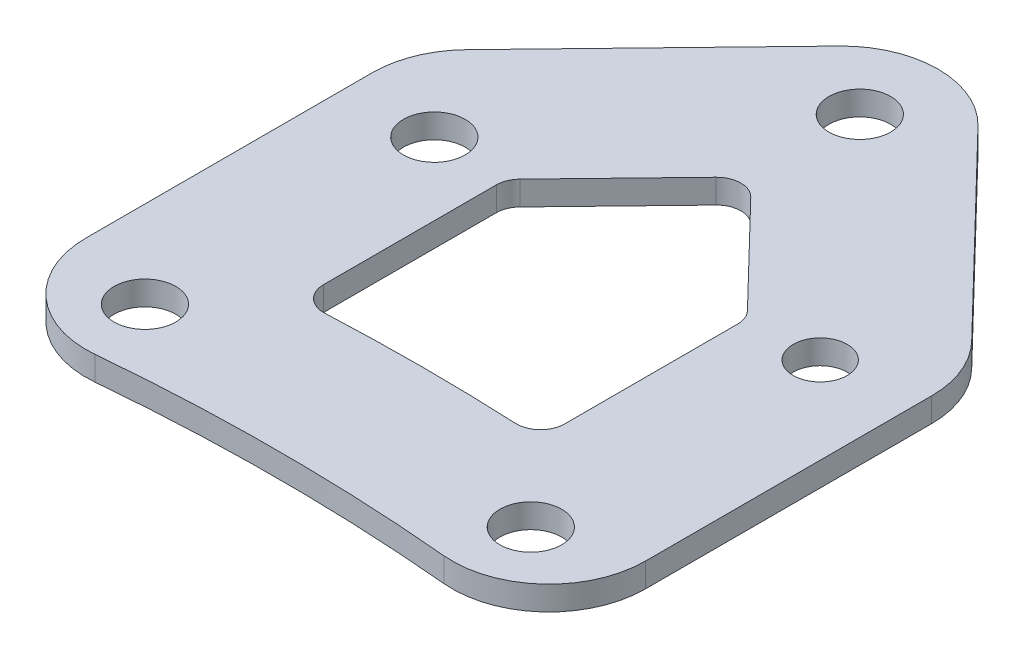
SolidWorks part; units mm, degrees
ref_plane "Front Plane" through (0, 0, 0) normal (0, 0, 1) x (1, 0, 0)
ref_plane "Top Plane" through (0, 0, 0) normal (0, 1, 0) x (1, 0, 0)
ref_plane "Right Plane" through (0, 0, 0) normal (1, 0, 0) x (0, 0, -1)
sketch "Sketch1" plane through (0, 0, 0) normal (0, 1, 0) x (1, 0, 0)
  line L1 (0, 0) -> (18.415, -19.05)
  line L2 (18.415, -19.05) -> (18.415, -47.625)
  line L4 (-18.415, -47.625) -> (-18.415, -19.05)
  line L5 (-18.415, -19.05) -> (0, 0)
  arc A0 (-18.415, -47.625) -> (18.415, -47.625) centre (0, -171.7322) cw
  dimension "D2" = 125.466
  dimension "D1" = 47.625
  dimension "D3" = 36.83
  dimension "D4" = 19.05
extrude "Boss-Extrude1" add sketch "Sketch1" along normal blind 1.5875
sketch "Sketch3" plane through (0, 1.5875, 0) normal (0, 1, 0) x (1, 0, 0)
  circle A0 centre (12.7, -42.2941) radius 2.032
  circle A1 centre (-12.7, -42.2941) radius 2.032
  circle A2 centre (-12.7, -23.2441) radius 2.032
  circle A3 centre (12.7, -23.2441) radius 1.778
  circle A4 centre (0, -7.9375) radius 2.032
  dimension "D1" = 4.064
  dimension "D2" = 3.556
  dimension "D3" = 7.9375
extrude "Cut-Extrude1" cut sketch "Sketch3" against normal through all
sketch "Sketch4" plane through (0, 1.5875, 0) normal (0, 1, 0) x (1, 0, 0)
  line L17 (7.9375, -47.625) -> (7.9375, -23.2863)
  line L18 (-7.9375, -23.2863) -> (-7.9375, -47.625)
  line L19 (7.9375, -23.2863) -> (0, -15.0751)
  line L20 (0, -15.0751) -> (-7.9375, -23.2863)
  line L21 (7.9375, -36.9748) -> (7.9375, -23.2863)
  line L22 (-7.9375, -23.2863) -> (-7.9375, -36.9748)
  line L23 (7.9375, -23.2863) -> (0, -15.0751)
  line L24 (0, -15.0751) -> (-7.9375, -23.2863)
  arc A2 (19.813, -38.2032) -> (-19.813, -38.2032) centre (0, -171.7322) ccw
  arc A3 (7.9375, -36.9748) -> (-7.9375, -36.9748) centre (0, -171.7322) ccw
  dimension "D1" = 10.4775
  dimension "D2" = 9.525
extrude "Cut-Extrude2" cut sketch "Sketch4" against normal through all
fillet "Fillet1" radius 6.35 5 edges at (-18.415, 0.7937, 47.625) (18.415, 0.7937, 47.625) (18.415, 0.7937, 19.05) (-18.415, 0.7937, 19.05) (0, 0.7937, 0)
fillet "Fillet2" radius 1.5875 5 edges at (-7.9375, 0.7937, 36.9748) (7.9375, 0.7937, 36.9748) (7.9375, 0.7937, 23.2863) (-7.9375, 0.7937, 23.2863) (0, 0.7937, 15.0751)
